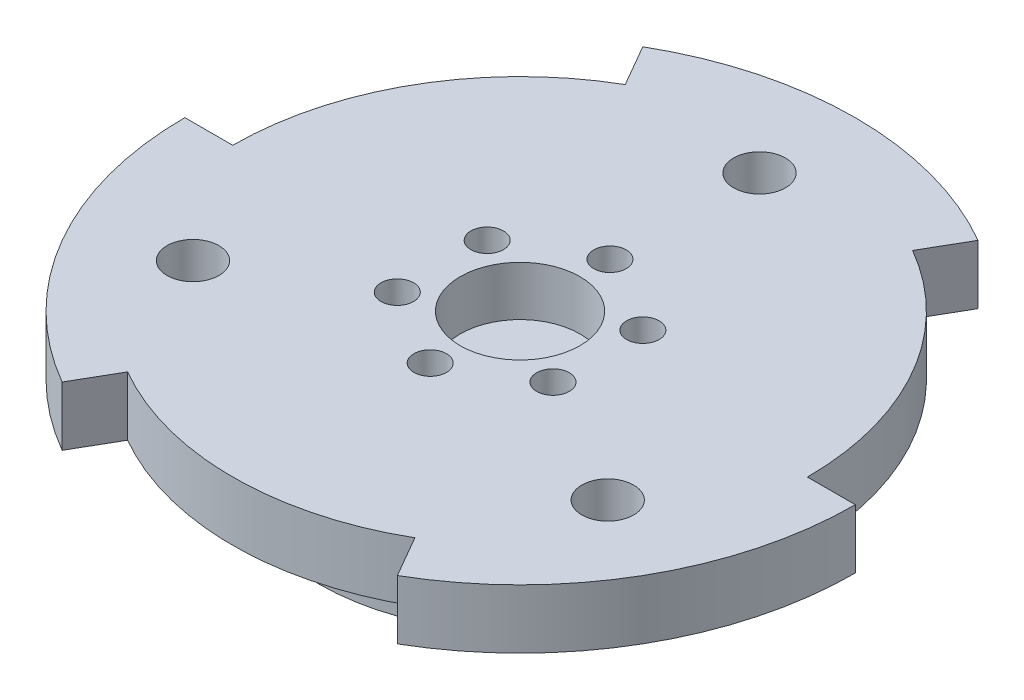
SolidWorks part; units mm, degrees
ref_plane "Front Plane" through (0, 0, 0) normal (0, 0, 1) x (1, 0, 0)
ref_plane "Top Plane" through (0, 0, 0) normal (0, 1, 0) x (1, 0, 0)
ref_plane "Right Plane" through (0, 0, 0) normal (1, 0, 0) x (0, 0, -1)
sketch "Sketch7" plane through (0, 0, 0) normal (0, 1, 0) x (1, 0, 0)
  line L1 (-11.3137, -11.3137) -> (11.3137, -11.3137)
  line L2 (-11.3137, -11.3137) -> (-11.3137, 11.3137)
  line L3 (-11.3137, 11.3137) -> (11.3137, 11.3137)
  line L4 (11.3137, -11.3137) -> (11.3137, 11.3137)
  line L5 (-11.3137, -11.3137) -> (11.3137, 11.3137) construction
  line L6 (-11.3137, 11.3137) -> (11.3137, -11.3137) construction
  circle A0 centre (0, 0) radius 16.1
  point P0 (0, 0)
  dimension "D1" = 32
extrude "Boss-Extrude2" add sketch "Sketch7" along normal blind 8.2 contours L1 L4 L3 L2 | A0 L4 L1 L2 L3 region at (0, 0, 0) region at (-15.6446, 0, 0)
sketch "Sketch1" plane through (0, 8.2, 0) normal (0, 1, 0) x (1, 0, 0)
  line L0 (0, 0) -> (0, 35.4208) construction
  line L1 (-20, -20) -> (20, -20)
  line L2 (-20, -20) -> (-20, 20)
  line L3 (-20, 20) -> (20, 20)
  line L4 (20, -20) -> (20, 20)
  line L5 (-20, -20) -> (20, 20) construction
  line L6 (-20, 20) -> (20, -20) construction
  line L7 (17.5, 30.3109) -> (15, 25.9808)
  line L8 (-17.5, 30.3109) -> (-15, 25.9808)
  line L9 (17.5, -30.3109) -> (15, -25.9808)
  line L10 (35, 0) -> (30, 0)
  line L11 (-35, 0) -> (-30, 0)
  line L12 (-17.5, -30.3109) -> (-15, -25.9808)
  circle A0 centre (0, 0) radius 6.25
  circle A1 centre (0, 25) radius 2.7073
  circle A2 centre (21.6506, -12.5) radius 2.7073
  circle A3 centre (-21.6506, -12.5) radius 2.7073
  circle A4 centre (0, 0) radius 30
  arc A5 (17.5, 30.3109) -> (-17.5, 30.3109) centre (0, 0) ccw
  arc A6 (17.5, -30.3109) -> (35, 0) centre (0, 0) ccw
  arc A7 (-35, 0) -> (-17.5, -30.3109) centre (0, 0) ccw
  point P0 (0, 0)
  point P18 (0, 0)
  point P21 (0, 35)
  point P34 (0, 0)
  dimension "D2" = 12.5
  dimension "D6" = 60
  dimension "D7" = 5
  dimension "D8" = 35
  dimension "D9" = 3
  dimension "D1" = 25
  dimension "D3" = 40
  dimension "D4" = 40
  dimension "D5" = 3
extrude "Boss-Extrude1" add sketch "Sketch1" along normal blind 5.18 contours L11 A7 L12 A4 | L9 A6 L10 A4 | L7 A5 L8 A4 | L2 A3 | L4 A2 | A1 | L2 A3 | L4 A2 | A0 | A4 region at (-21.9823, 8.2, 12.5) region at (-19.5694, 8.2, 12.5) region at (19.5694, 8.2, 12.5) region at (21.9823, 8.2, 12.5) region at (0, 8.2, -31.0964) region at (26.9303, 8.2, 15.5482) region at (-26.9303, 8.2, 15.5482) region at (0, 8.2, 0) region at (0, 8.2, -25)
sketch "Sketch5" [suppressed] plane through (0, 0, 0) normal (1, 0, 0) x (0, 0, -1)
  line L0 (-10.331, 15) -> (10.331, 0) construction
  line L1 (10, 5) -> (-10, 5)
  line L2 (10, 5) -> (10, 10)
  line L3 (10, 10) -> (-10, 10)
  line L4 (-10, 5) -> (-10, 10)
  line L5 (10, 5) -> (-10, 10) construction
  line L6 (10, 10) -> (-10, 5) construction
  line L7 (20, 7.5) -> (-20, 7.5) construction
  line L8 (20, 15) -> (20, 0) construction
  line L9 (-20, 15) -> (-20, 0) construction
  line L10 (-10.3541, 15) -> (-10.3078, 15) construction
  line L11 (-10.3541, 0) -> (20, 0) construction
  point P0 (0, 7.5)
  dimension "D1" = 20
  dimension "D2" = 5
sketch "Sketch3" [suppressed] plane through (0, 0, -20) normal (0, 0, -1) x (-1, 0, 0)
  line L3 (15.1539, 15) -> (15.1539, 3) construction
  line L4 (20, 15) -> (10.3078, 15) construction
  circle A0 centre (15.1539, 3) radius 1.6
  dimension "D2" = 3.2
  dimension "D1" = 12
sketch "Sketch2" [suppressed] plane through (0, 0, 20) normal (0, 0, 1) x (1, 0, 0)
  line L0 (0, 27.8717) -> (0, -11.9207) construction
  line L1 (20, 2) -> (10, 2)
  line L3 (10, 2) -> (10, 0)
  line L4 (-20, 0) -> (20, 0) construction
  line L5 (20, 15) -> (20, 0) construction
  circle A0 centre (10, 2) radius 1.6
  circle A1 centre (-10, 2) radius 1.6
  dimension "D3" = 3.2
  dimension "D1" = 10
  dimension "D2" = 2
sketch "Sketch6" plane through (0, 13.38, 0) normal (0, 1, 0) x (1, 0, 0)
  circle A9 centre (0, -9.385) radius 1.7
  circle A10 centre (-8.1276, -4.6925) radius 1.7
  circle A11 centre (-8.1276, 4.6925) radius 1.7
  circle A12 centre (0, 9.385) radius 1.7
  circle A13 centre (8.1276, 4.6925) radius 1.7
  circle A14 centre (8.1276, -4.6925) radius 1.7
  point P16 (0, 0)
  dimension "D2" = 9.385
  dimension "D1" = 3.4
  dimension "D3" = 9.385
extrude "Cut-Extrude1" cut sketch "Sketch6" along normal through all and the other way through all
fillet "Fillet2" [suppressed] radius 5
sketch "Sketch9" plane through (0, 13.38, 0) normal (0, 1, 0) x (1, 0, 0)
  line L6 (-30, 0) -> (-35, 0)
  line L7 (-17.5, -30.3109) -> (-15, -25.9808)
  line L8 (15, -25.9808) -> (17.5, -30.3109)
  line L9 (35, 0) -> (30, 0)
  line L10 (15, 25.9808) -> (17.5, 30.3109)
  line L11 (-17.5, 30.3109) -> (-15, 25.9808)
  line L12 (-30, 0) -> (-35, 0)
  line L13 (-17.5, -30.3109) -> (-15, -25.9808)
  line L14 (15, -25.9808) -> (17.5, -30.3109)
  line L15 (35, 0) -> (30, 0)
  line L16 (15, 25.9808) -> (17.5, 30.3109)
  line L17 (-17.5, 30.3109) -> (-15, 25.9808)
  arc A6 (-35, 0) -> (-17.5, -30.3109) centre (0, 0) ccw
  arc A7 (-15, -25.9808) -> (15, -25.9808) centre (0, 0) ccw
  arc A8 (17.5, -30.3109) -> (35, 0) centre (0, 0) ccw
  arc A9 (30, 0) -> (15, 25.9808) centre (0, 0) ccw
  arc A10 (17.5, 30.3109) -> (-17.5, 30.3109) centre (0, 0) ccw
  arc A11 (-15, 25.9808) -> (-30, 0) centre (0, 0) ccw
  arc A12 (-35, 0) -> (-17.5, -30.3109) centre (0, 0) ccw
  arc A13 (-15, -25.9808) -> (15, -25.9808) centre (0, 0) ccw
  arc A14 (17.5, -30.3109) -> (35, 0) centre (0, 0) ccw
  arc A15 (30, 0) -> (15, 25.9808) centre (0, 0) ccw
  arc A16 (17.5, 30.3109) -> (-17.5, 30.3109) centre (0, 0) ccw
  arc A17 (-15, 25.9808) -> (-30, 0) centre (0, 0) ccw
  circle M14 centre (8.1276, -4.6925) radius 1.7
  circle M15 centre (8.1276, 4.6925) radius 1.7
  circle M16 centre (0, 9.385) radius 1.7
  circle M17 centre (-8.1276, 4.6925) radius 1.7
  circle M18 centre (-8.1276, -4.6925) radius 1.7
  circle M31 centre (21.6506, -12.5) radius 2.7073
  circle M32 centre (0, 25) radius 2.7073
  circle M33 centre (-21.6506, -12.5) radius 2.7073
  circle M34 centre (0, 0) radius 6.25
  dimension "D1" = 0
extrude "Cut-Extrude2" cut sketch "Sketch9" against normal through all contours M33 | M34 | M31 | M32 | M14 | M15 | M16 | M17 | M18 region at (8.1276, 13.38, 4.6925) region at (8.1276, 13.38, -4.6925) region at (0, 13.38, -9.385) region at (-8.1276, 13.38, -4.6925) region at (-8.1276, 13.38, 4.6925) region at (21.6506, 13.38, 12.5) region at (0, 13.38, -25) region at (-21.6506, 13.38, 12.5) region at (0, 13.38, 0)
sketch "Sketch10" plane through (0, 8.2, 0) normal (0, -1, 0) x (1, 0, 0)
  circle A1 centre (0, 0) radius 16.1 construction
  circle A3 centre (0, 0) radius 21
  circle M2 centre (0, 0) radius 16.1
  dimension "D1" = 42
extrude "Boss-Extrude3" add sketch "Sketch10" along normal blind 9 contours A3 M2 region at (-20.406, 8.2, 0)
chamfer "Chamfer1" distance 1.5 angle 45 1 edges at (0, -0.8, -16.1)
sketch "Sketch11" plane through (0, 8.2, 0) normal (0, -1, 0) x (1, 0, 0)
  line L6 (-35, 0) -> (-30, 0)
  line L7 (-15, -25.9808) -> (-17.5, -30.3109)
  line L8 (17.5, -30.3109) -> (15, -25.9808)
  line L9 (30, 0) -> (35, 0)
  line L10 (17.5, 30.3109) -> (15, 25.9808)
  line L11 (-15, 25.9808) -> (-17.5, 30.3109)
  line L12 (-35, 0) -> (-30, 0)
  line L13 (-15, -25.9808) -> (-17.5, -30.3109)
  line L14 (17.5, -30.3109) -> (15, -25.9808)
  line L15 (30, 0) -> (35, 0)
  line L16 (17.5, 30.3109) -> (15, 25.9808)
  line L17 (-15, 25.9808) -> (-17.5, 30.3109)
  circle A0 centre (21.6506, 12.5) radius 2.7073 construction
  circle A1 centre (0, -25) radius 2.7073 construction
  circle A2 centre (-21.6506, 12.5) radius 2.7073 construction
  circle A3 centre (21.6506, 12.5) radius 2.7073
  circle A4 centre (0, -25) radius 2.7073
  circle A5 centre (-21.6506, 12.5) radius 2.7073
  arc A6 (-30, 0) -> (-15, -25.9808) centre (0, 0) ccw
  arc A7 (-17.5, -30.3109) -> (17.5, -30.3109) centre (0, 0) ccw
  arc A8 (15, -25.9808) -> (30, 0) centre (0, 0) ccw
  arc A9 (35, 0) -> (17.5, 30.3109) centre (0, 0) ccw
  arc A10 (15, 25.9808) -> (-15, 25.9808) centre (0, 0) ccw
  arc A11 (-17.5, 30.3109) -> (-35, 0) centre (0, 0) ccw
  arc A12 (-30, 0) -> (-15, -25.9808) centre (0, 0) ccw
  arc A13 (-17.5, -30.3109) -> (17.5, -30.3109) centre (0, 0) ccw
  arc A14 (15, -25.9808) -> (30, 0) centre (0, 0) ccw
  arc A15 (35, 0) -> (17.5, 30.3109) centre (0, 0) ccw
  arc A16 (15, 25.9808) -> (-15, 25.9808) centre (0, 0) ccw
  arc A17 (-17.5, 30.3109) -> (-35, 0) centre (0, 0) ccw
  dimension "D1" = 0
extrude "Boss-Extrude4" add sketch "Sketch11" along normal blind 1
